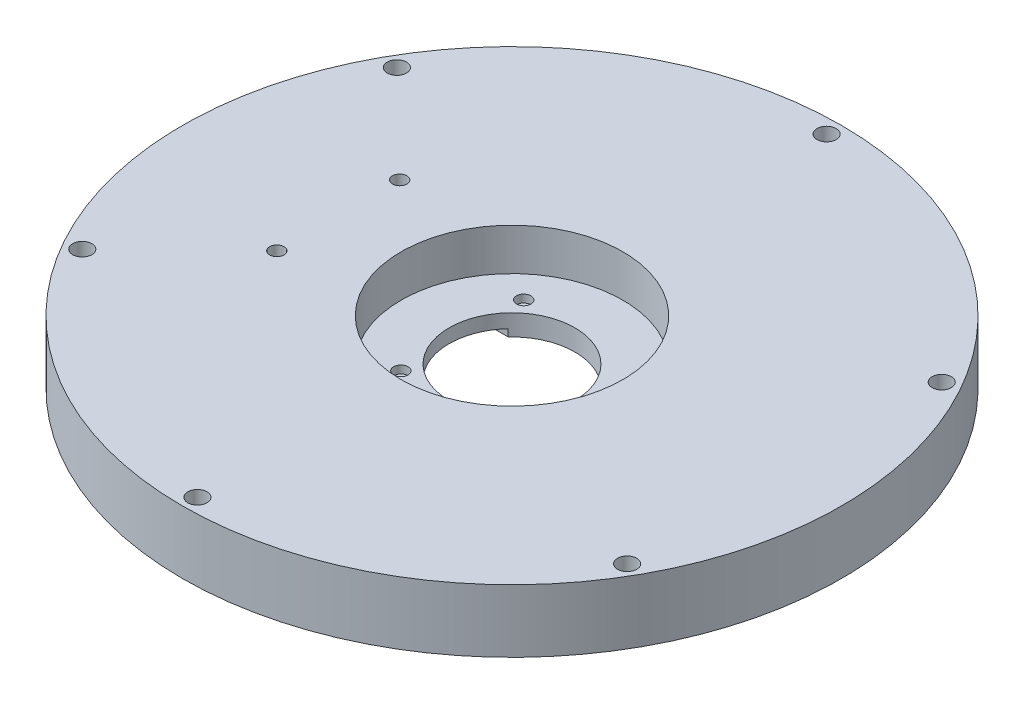
SolidWorks part; units mm, degrees
ref_plane "Front Plane" through (0, 0, 0) normal (0, 0, 1) x (1, 0, 0)
ref_plane "Top Plane" through (0, 0, 0) normal (0, 1, 0) x (1, 0, 0)
ref_plane "Right Plane" through (0, 0, 0) normal (1, 0, 0) x (0, 0, -1)
sketch "Sketch1" plane through (0, 0, 0) normal (0, 1, 0) x (1, 0, 0)
  line L0 (0, 55) -> (0, 50) construction
  circle A0 centre (0, 0) radius 50
  circle A1 centre (0, 0) radius 10.5
  circle A2 centre (0, 0) radius 55
  circle A3 centre (0, 52.5) radius 1.6
  circle A4 centre (45.4663, 26.25) radius 1.6
  circle A5 centre (45.4663, -26.25) radius 1.6
  circle A6 centre (0, -52.5) radius 1.6
  circle A7 centre (-45.4663, -26.25) radius 1.6
  circle A8 centre (-45.4663, 26.25) radius 1.6
  point P21 (0, 0)
  dimension "D1" = 100
  dimension "D2" = 21
  dimension "D3" = 110
  dimension "D4" = 3.2
  dimension "D5" = 6
extrude "Boss-Extrude1" add sketch "Sketch1" against normal blind 7.5 contours A2 A0 region at (-53.4444, 0, 0)
extrude "Boss-Extrude2" add sketch "Sketch2<3>" against normal blind 7.5 contours A0 A1 region at (-48.5858, 0, 0)
sketch "Sketch2<3>" plane through (0, 0, 0) normal (0, 1, 0) x (1, 0, 0) same geometry as "Sketch1"
sketch "Sketch2" plane through (0, 0, 0) normal (0, 1, 0) x (1, 0, 0)
  line L0 (0, -10.25) -> (0, 10.25) construction
  line L1 (0, 10.25) -> (-8.3, 10.25) construction
  line L2 (-8.3, 10.25) -> (-29, 10.25) construction
  line L3 (0, 0) -> (50000, 0) construction
  line L4 (-8.3, -10.25) -> (-29, -10.25) construction
  line L5 (0, -10.25) -> (-8.3, -10.25) construction
  circle A0 centre (-29, 10.25) radius 0.5
  circle A1 centre (-8.3, 10.25) radius 0.5
  circle A2 centre (-8.3, -10.25) radius 0.5
  circle A3 centre (-29, -10.25) radius 0.5
  circle A4 centre (-29, 10.25) radius 1.2
  circle A5 centre (-8.3, 10.25) radius 1.2
  circle A6 centre (-8.3, -10.25) radius 1.2
  circle A7 centre (-29, -10.25) radius 1.2
  point P12 (0, 0)
  dimension "D4" = 1
  dimension "D5" = 2.4
  dimension "D1" = 10.25
  dimension "D2" = 8.3
  dimension "D3" = 20.7
extrude "Cut-Extrude1" cut sketch "Sketch2" against normal up to surface (7.5 mm away) contours A0 | A1 | A2 | A3 | A0 | A1 region at (-29, 0, -10.25) region at (-8.3, 0, -10.25) region at (-8.3, 0, 10.25) region at (-29, 0, 10.25) up to face at (0, -7.5, -50.9)
extrude "Cut-Extrude2" cut sketch "Sketch2<3>" against normal offset from surface (5.3 mm away) 2.2 contours A4 A0 | A5 A1 | A6 A2 | A7 A3 region at (-30.1661, 0, -10.25) region at (-9.4661, 0, -10.25) region at (-9.4661, 0, 10.25) region at (-30.1661, 0, 10.25) up to face at (-8.3, -7.5, -9.75)
sketch "Sketch2<3>" plane through (0, 0, 0) normal (0, 1, 0) x (1, 0, 0) same geometry as "Sketch2"
sketch "Sketch3" plane through (0, -7.5, 0) normal (0, -1, 0) x (1, 0, 0)
  line L0 (0, 0) -> (-34.6, 0) construction
  line L1 (-34.6, -7.1) -> (-34.6, 7.1)
  line L2 (-34.6, 7.1) -> (0, 7.1)
  line L3 (0, 7.1) -> (0, -7.1)
  line L4 (0, -7.1) -> (-34.6, -7.1)
  point P7 (-34.6, 0)
  circle M8 centre (0, 0) radius 10.5
  dimension "D1" = 14.2
  dimension "D2" = 34.6
extrude "Cut-Extrude3" cut sketch "Sketch3" against normal blind 1.2 contours L0 L2 L1 M8 | L0 L1 L4 M8 region at (-22.1037, -7.5, -3.6134) region at (-22.1037, -7.5, 3.6134)
sketch "Sketch4" plane through (0, 0, 0) normal (0, 1, 0) x (1, 0, 0)
  circle A0 centre (0, 0) radius 18.5
  dimension "D1" = 37
extrude "Cut-Extrude4" cut sketch "Sketch4" against normal blind 4
sketch "Sketch5" plane through (0, 0, 0) normal (0, 1, 0) x (1, 0, 0)
  circle A0 centre (0, 0) radius 18.5
  circle A1 centre (0, 0) radius 55
  circle A2 centre (0, 0) radius 55 construction
  circle A3 centre (-45.4663, 26.25) radius 1.6
  circle A4 centre (-45.4663, 26.25) radius 1.6 construction
  circle A5 centre (0, 52.5) radius 1.6
  circle A6 centre (45.4663, 26.25) radius 1.6
  circle A7 centre (45.4663, -26.25) radius 1.6
  circle A8 centre (0, -52.5) radius 1.6
  circle A9 centre (-45.4663, -26.25) radius 1.6
  circle A10 centre (-29, 10.25) radius 1.2
  circle A11 centre (-8.3, 10.25) radius 1.2
  circle A12 centre (-8.3, -10.25) radius 1.2
  circle A13 centre (-29, -10.25) radius 1.2
  circle A14 centre (-29, 10.25) radius 1.2 construction
  point P23 (0, 0)
  circle M7 centre (-29, 10.25) radius 1.2
  circle M8 centre (0, 52.5) radius 1.6
  circle M9 centre (-45.4663, 26.25) radius 1.6
  circle M10 centre (-45.4663, -26.25) radius 1.6
  circle M11 centre (0, -52.5) radius 1.6
  circle M12 centre (45.4663, -26.25) radius 1.6
  circle M13 centre (45.4663, 26.25) radius 1.6
  circle M14 centre (0, 0) radius 55
  circle M15 centre (-29, -10.25) radius 1.2
  dimension "D1" = 37
  dimension "D2" = 6
extrude "Boss-Extrude3" add sketch "Sketch5" along normal blind 3 contours A0 M14 M8 M10 M12 M15 M13 M11 M9 M7 region at (-53.4444, 0, 0)
